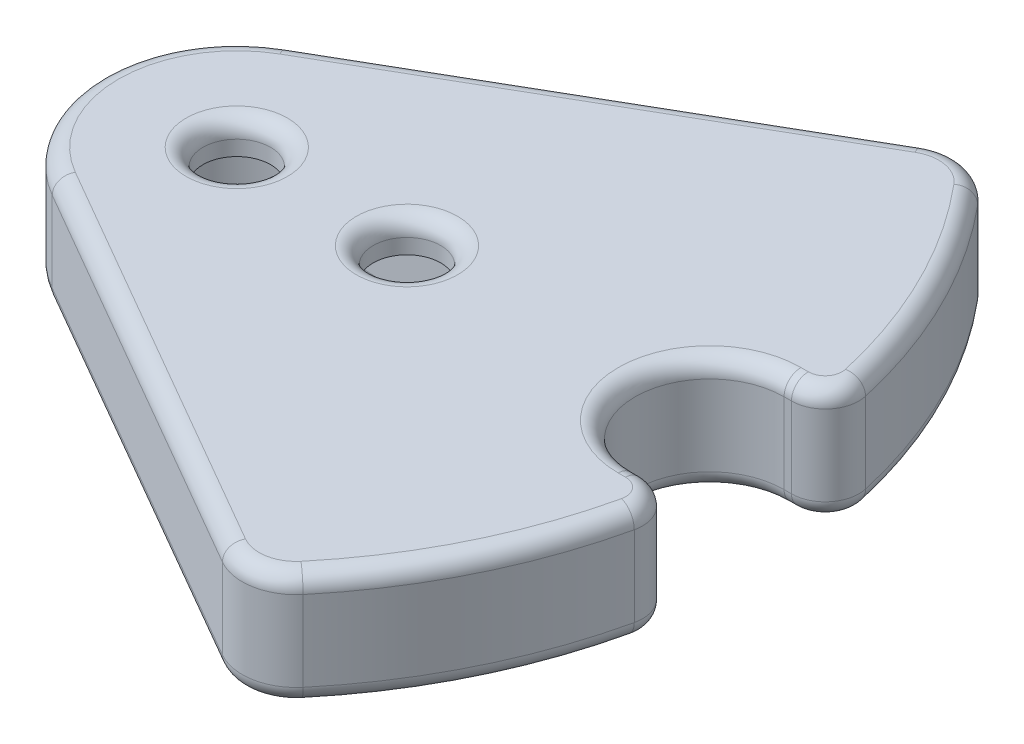
SolidWorks part; units mm, degrees
ref_plane "Front Plane" through (0, 0, 0) normal (0, 0, 1) x (1, 0, 0)
ref_plane "Top Plane" through (0, 0, 0) normal (0, 1, 0) x (1, 0, 0)
ref_plane "Right Plane" through (0, 0, 0) normal (1, 0, 0) x (0, 0, -1)
sketch "Sketch1" plane through (0, 0, 0) normal (0, 1, 0) x (1, 0, 0)
  line L0 (2.2864, 2.65) -> (14.1103, 1.997)
  line L1 (2.2864, -2.65) -> (14.1103, -1.997)
  line L2 (0, 0) -> (14, 0) construction
  line L3 (16, 0) -> (18.725, 0) construction
  line L5 (18.725, 0) -> (24.725, 0) construction
  line L6 (22.225, 3.5) -> (24.476, 3.5)
  line L7 (22.225, -3.5) -> (24.476, -3.5)
  line L8 (-3.175, -5.4993) -> (17.5193, -17.4471)
  line L9 (-3.175, 5.4993) -> (17.5193, 17.4471)
  line L10 (-3.175, 5.4993) -> (0, 0) construction
  line L11 (0, 0) -> (-3.175, -5.4993) construction
  circle A0 centre (0, 0) radius 3.5 construction
  arc A1 (14.1103, 1.997) -> (14.1103, -1.997) centre (14, 0) cw
  arc A2 (2.2864, 2.65) -> (2.2864, -2.65) centre (0, 0) ccw
  circle A3 centre (14, 0) radius 0.5 construction
  circle A4 centre (12, 0) radius 0.5 construction
  circle A5 centre (10, 0) radius 0.5 construction
  circle A6 centre (8, 0) radius 0.5 construction
  circle A7 centre (6, 0) radius 0.5 construction
  circle A8 centre (4, 0) radius 0.5 construction
  arc A9 (17.5193, 17.4471) -> (24.476, 3.5) centre (0, 0) cw
  arc A11 (22.225, 3.5) -> (22.225, -3.5) centre (22.225, 0) ccw
  arc A15 (17.5193, -17.4471) -> (24.476, -3.5) centre (0, 0) ccw
  arc A16 (-6.35, 0) -> (-3.175, -5.4993) centre (0, 0) ccw
  arc A17 (-6.35, 0) -> (-3.175, 5.4993) centre (0, 0) cw
  arc A18 (-24.725, 0) -> (17.5193, -17.4471) centre (0, 0) ccw construction
  arc A19 (-24.725, 0) -> (17.5193, 17.4471) centre (0, 0) cw construction
  point P4 (16, 0)
  point P6 (-3.5, 0)
  dimension "D1" = 7
  dimension "D5" = 1
  dimension "D8" = 120
  dimension "D10" = 3.5
  dimension "D4" = 2
  dimension "D11" = 6.35
  dimension "D2" = 19.5
  dimension "D3" = 5.3
  dimension "D7" = 2
  dimension "D9" = 6
  dimension "D12" = 22.225
  dimension "D6" = 6
extrude "Boss-Extrude1" add sketch "Sketch1" along normal blind 4.5
fillet "Fillet4" radius 2.54 2 edges at (17.5193, 2.25, 17.4471) (17.5193, 2.25, -17.4471)
sketch "Sketch2" plane through (0, 4.5, 0) normal (0, 1, 0) x (1, 0, 0)
  line L0 (0, 0) -> (16, 0) construction
  line L5 (-3.175, -5.4993) -> (15.7523, -16.427)
  line L6 (24.476, -3.5) -> (22.225, -3.5)
  line L7 (22.225, 3.5) -> (24.476, 3.5)
  line L10 (24.476, -3.5) -> (22.225, -3.5)
  line L11 (22.225, 3.5) -> (24.476, 3.5)
  line L12 (-3.175, -5.4993) -> (15.7523, -16.427)
  line L13 (15.7523, 16.427) -> (-3.175, 5.4993)
  line L14 (15.7523, 16.427) -> (-3.175, 5.4993)
  circle A0 centre (0, 0) radius 1.5875
  circle A1 centre (8, 0) radius 1.5875
  arc A2 (14.1103, -1.997) -> (14.1103, 1.997) centre (14, 0) ccw construction
  arc A7 (24.476, 3.5) -> (18.9712, 15.8562) centre (0, 0) ccw
  arc A8 (24.476, 3.5) -> (18.9712, 15.8562) centre (0, 0) ccw
  arc A9 (-3.175, 5.4993) -> (-3.175, -5.4993) centre (0, 0) ccw
  arc A10 (-3.175, 5.4993) -> (-3.175, -5.4993) centre (0, 0) ccw
  arc A11 (18.9712, -15.8562) -> (24.476, -3.5) centre (0, 0) ccw
  arc A13 (22.225, 3.5) -> (22.225, -3.5) centre (22.225, 0) ccw
  arc A15 (15.7523, -16.427) -> (18.9712, -15.8562) centre (17.0223, -14.2273) ccw
  arc A19 (18.9712, -15.8562) -> (24.476, -3.5) centre (0, 0) ccw
  arc A21 (22.225, 3.5) -> (22.225, -3.5) centre (22.225, 0) ccw
  arc A22 (15.7523, -16.427) -> (18.9712, -15.8562) centre (17.0223, -14.2273) ccw
  arc A23 (18.9712, 15.8562) -> (15.7523, 16.427) centre (17.0223, 14.2273) ccw
  arc A24 (18.9712, 15.8562) -> (15.7523, 16.427) centre (17.0223, 14.2273) ccw
  point P15 (8, 0)
  dimension "D2" = 3.175
  dimension "D3" = 3.175
  dimension "D1" = 0
extrude "Boss-Extrude2" add sketch "Sketch2" along normal offset from surface (1.5 mm away) 6 up to face at (15.1755, 0, 0)
sketch "Sketch3" plane through (0, 0, 0) normal (0, -1, 0) x (1, 0, 0)
  line L4 (24.476, -3.5) -> (22.225, -3.5)
  line L5 (22.225, 3.5) -> (24.476, 3.5)
  line L6 (-3.175, -5.4993) -> (15.7523, -16.427)
  line L7 (-3.175, -5.4993) -> (15.7523, -16.427)
  line L8 (24.476, -3.5) -> (22.225, -3.5)
  line L9 (22.225, 3.5) -> (24.476, 3.5)
  line L10 (15.7523, 16.427) -> (-3.175, 5.4993)
  line L11 (15.7523, 16.427) -> (-3.175, 5.4993)
  arc A4 (24.476, 3.5) -> (18.9712, 15.8562) centre (0, 0) ccw
  arc A5 (24.476, 3.5) -> (18.9712, 15.8562) centre (0, 0) ccw
  arc A6 (-3.175, 5.4993) -> (-3.175, -5.4993) centre (0, 0) ccw
  arc A7 (18.9712, -15.8562) -> (24.476, -3.5) centre (0, 0) ccw
  arc A8 (22.225, 3.5) -> (22.225, -3.5) centre (22.225, 0) ccw
  arc A9 (-3.175, 5.4993) -> (-3.175, -5.4993) centre (0, 0) ccw
  arc A13 (18.9712, -15.8562) -> (24.476, -3.5) centre (0, 0) ccw
  arc A14 (22.225, 3.5) -> (22.225, -3.5) centre (22.225, 0) ccw
  arc A15 (18.9712, 15.8562) -> (15.7523, 16.427) centre (17.0223, 14.2273) ccw
  arc A16 (18.9712, 15.8562) -> (15.7523, 16.427) centre (17.0223, 14.2273) ccw
  arc A17 (15.7523, -16.427) -> (18.9712, -15.8562) centre (17.0223, -14.2273) ccw
  arc A18 (15.7523, -16.427) -> (18.9712, -15.8562) centre (17.0223, -14.2273) ccw
  dimension "D1" = 0
extrude "Cut-Extrude1" cut sketch "Sketch3" against normal blind 0.635
fillet "Fillet1" radius 1.5875 2 edges at (24.476, 3.3175, 3.5) (24.476, 3.3175, -3.5)
fillet "Fillet2" radius 0.7937 16 edges at (18.725, 0.635, 0) (22.3981, 0.635, -3.5) (23.8111, 0.635, -4.096) (22.1665, 0.635, -10.9532) (22.1665, 0.635, 10.9532) (23.8111, 0.635, 4.096) (22.3981, 0.635, 3.5) (-3.5, 0.635, 0) (8.1983, 0.635, -2.3235) (16, 0.635, 0) (8.1983, 0.635, 2.3235) (6.2887, 0.635, -10.9631) (-6.35, 0.635, 0) (6.2887, 0.635, 10.9631) (17.4658, 0.635, -16.7282) (17.4658, 0.635, 16.7282)
fillet "Fillet3" radius 0.7937 14 edges at (22.1665, 6, -10.9532) (23.8111, 6, -4.096) (22.3981, 6, -3.5) (18.725, 6, 0) (22.3981, 6, 3.5) (23.8111, 6, 4.096) (22.1665, 6, 10.9532) (0, 6, -1.5875) (8, 6, -1.5875) (6.2887, 6, 10.9631) (-6.35, 6, 0) (6.2887, 6, -10.9631) (17.4658, 6, 16.7282) (17.4658, 6, -16.7282)
